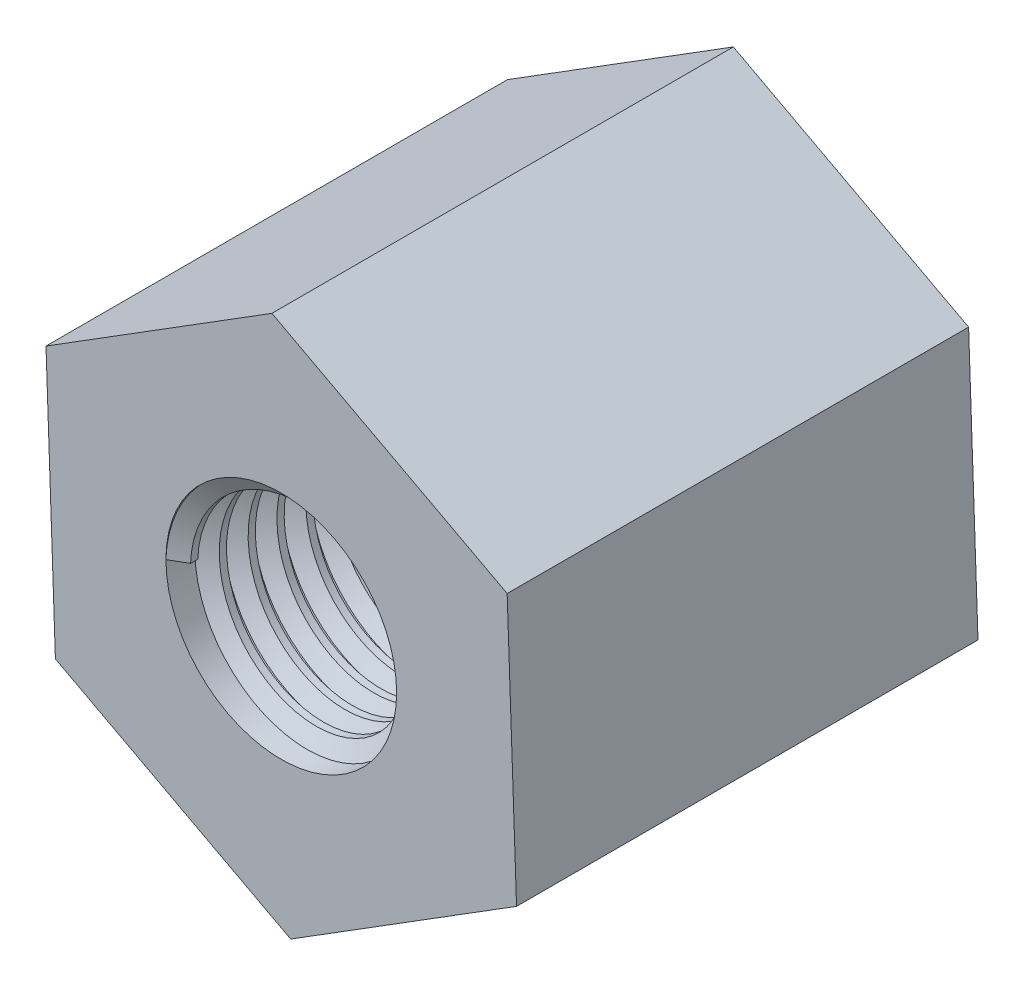
SolidWorks part; units mm, degrees
ref_plane "Front Plane" through (0, 0, 0) normal (0, 0, 1) x (1, 0, 0)
ref_plane "Top Plane" through (0, 0, 0) normal (0, 1, 0) x (1, 0, 0)
ref_plane "Right Plane" through (0, 0, 0) normal (1, 0, 0) x (0, 0, -1)
sketch "Sketch1" plane through (0, 0, 0) normal (0, 0, 1) x (1, 0, 0)
  line L1 (10.1973, -5.4173) -> (9.7902, 6.1225)
  line L2 (9.7902, 6.1225) -> (-0.4071, 11.5398)
  line L3 (-0.4071, 11.5398) -> (-10.1973, 5.4173)
  line L4 (-10.1973, 5.4173) -> (-9.7902, -6.1225)
  line L5 (-9.7902, -6.1225) -> (0.4071, -11.5398)
  line L6 (0.4071, -11.5398) -> (10.1973, -5.4173)
  circle A0 centre (0, 0) radius 10 construction
  circle A1 centre (0, 0) radius 5
  dimension "D1" = 20
  dimension "D2" = 10
extrude "Boss-Extrude1" add sketch "Sketch1" along normal blind 20
thread "Thread1" pitch 1.25 method extrude profile "Thread Profile1" start angle 0, offset 0, length 20, pitch 1.25, diameter 10
ref_plane "Plane1" through (-5, 0, 20) normal (0, -1, 0) x (-1, 0, 0)
sketch "Thread Profile1" plane through (-5, 0, 20) normal (0, -1, 0) x (-1, 0, 0)
  line L0 (0, 0) -> (0, 1.25) construction
  line L11 (0, 0) -> (0, 1.0937)
  line L12 (0, 1.0937) -> (-0.6766, 0.7031)
  line L13 (-0.6766, 0.7031) -> (-0.6766, 0.3906)
  line L15 (-0.6766, 0.3906) -> (0, 0)
  line L17 (-0.6766, 0.5469) -> (0, 0.5469) construction
  point P2 (0, 0)
  dimension "Pitch" = 1.25
  dimension "Profile_Angle" = 60
  dimension "Profile_Land" = 0.3125
  dimension "Profile_Height" = 0.6766
